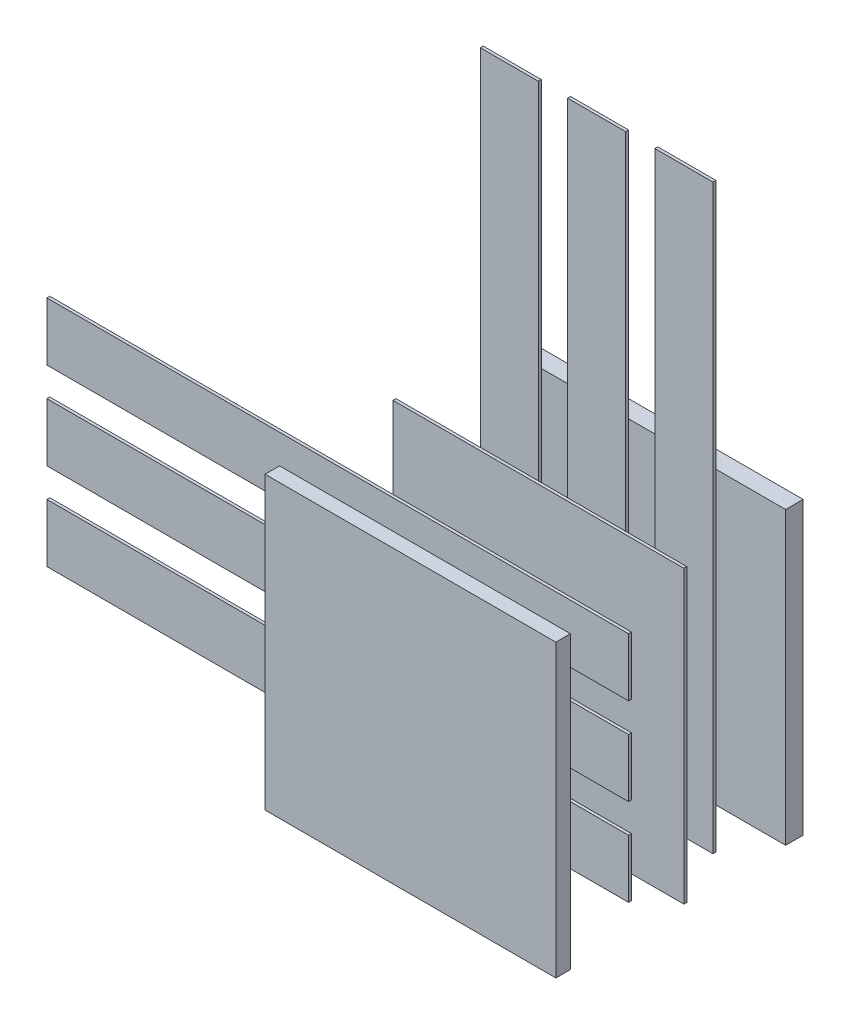
SolidWorks part; units mm, degrees
note: The reader was unsure of these and kept them because the rebuilt part matched: shared geometry of "Szkic1<2>", "Szkic1<3>".
ref_plane "Płaszczyzna przednia" through (0, 0, 0) normal (0, 0, 1) x (1, 0, 0)
ref_plane "Płaszczyzna górna" through (0, 0, 0) normal (0, 1, 0) x (1, 0, 0)
ref_plane "Płaszczyzna prawa" through (0, 0, 0) normal (1, 0, 0) x (0, 0, -1)
sketch "Szkic1" plane through (0, 0, 0) normal (0, 0, 1) x (1, 0, 0)
  line L1 (-50, 50) -> (50, 50)
  line L2 (-50, 50) -> (-50, -50)
  line L3 (-50, -50) -> (50, -50)
  line L4 (50, 50) -> (50, -50)
  point P4 (0, 50)
  point P6 (-50, 0)
  dimension "D1" = 100
sketch "Szkic2" plane through (0, 0, 0) normal (0, 0, 1) x (1, 0, 0)
  line L0 (-50, -50) -> (50, -50) construction
  line L1 (-10, -50) -> (10, -50)
  line L2 (-10, -50) -> (-10, 150)
  line L3 (-10, 150) -> (10, 150)
  line L4 (10, -50) -> (10, 150)
  line L5 (-50, 50) -> (50, 50) construction
  line L6 (-40, -50) -> (-40, 150)
  line L7 (-40, -50) -> (-20, -50)
  line L8 (-20, -50) -> (-20, 150)
  line L9 (-40, 150) -> (-20, 150)
  line L10 (-10, -50) -> (-40, -50) construction
  line L11 (20, -50) -> (20, 150)
  line L12 (20, -50) -> (40, -50)
  line L13 (40, -50) -> (40, 150)
  line L14 (20, 150) -> (40, 150)
  line L15 (-10, -50) -> (20, -50) construction
  point P6 (0, 150)
  dimension "D1" = 20
  dimension "D2" = 100
  dimension "D4" = 30
  dimension "D6" = 30
  dimension "D3" = 2
  dimension "D5" = 2
extrude "Dodanie-wyciągnięcie1" add sketch "Szkic1" along normal blind 6
extrude "Dodanie-wyciągnięcie2" add sketch "Szkic1<2>" along normal blind 1 from offset 40 separate body
sketch "Szkic1<2>" plane through (0, 0, 0) normal (0, 0, 1) x (1, 0, 0) same geometry as "Szkic1"
extrude "Dodanie-wyciągnięcie3" add sketch "Szkic1<3>" along normal blind 5 from offset 80 separate body
sketch "Szkic1<3>" plane through (0, 0, 0) normal (0, 0, 1) x (1, 0, 0) same geometry as "Szkic1"
sketch "Szkic4" plane through (0, 0, 0) normal (0, 0, -1) x (-1, 0, 0)
  line L0 (150, -10) -> (150, 10)
  line L1 (150, -10) -> (-50, -10)
  line L2 (-50, -10) -> (-50, 10)
  line L3 (150, 10) -> (-50, 10)
  line L4 (150, -40) -> (-50, -40)
  line L5 (150, -40) -> (150, -20)
  line L6 (150, -20) -> (-50, -20)
  line L7 (-50, -40) -> (-50, -20)
  line L8 (150, 20) -> (-50, 20)
  line L9 (150, 20) -> (150, 40)
  line L10 (150, 40) -> (-50, 40)
  line L11 (-50, 20) -> (-50, 40)
  line L12 (-50, -50) -> (-50, 50) construction
  point P15 (-50, 0)
  dimension "D1" = 10
  dimension "D2" = 10
  dimension "D3" = 20
  dimension "D4" = 200
extrude "Dodanie-wyciągnięcie5" add sketch "Szkic2" along normal blind 1 from offset 20 separate body
extrude "Dodanie-wyciągnięcie6" add sketch "Szkic4" along normal blind 1 from offset 60 separate body offset against normal yes
